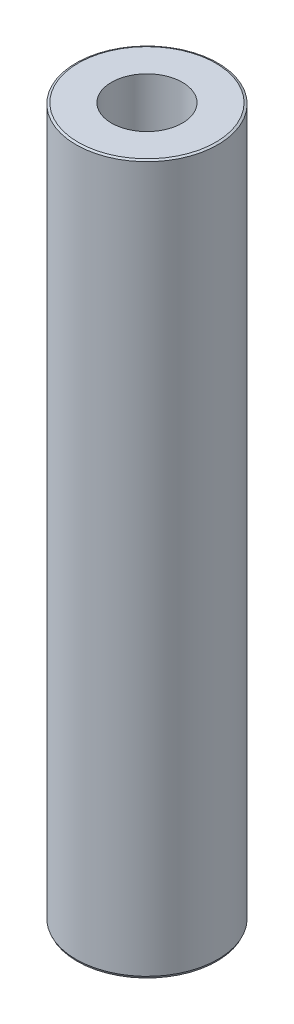
SolidWorks part; units mm, degrees
ref_plane "Front Plane" through (0, 0, 0) normal (0, 0, 1) x (1, 0, 0)
ref_plane "Top Plane" through (0, 0, 0) normal (0, 1, 0) x (1, 0, 0)
ref_plane "Right Plane" through (0, 0, 0) normal (1, 0, 0) x (0, 0, -1)
sketch "Sketch1" plane through (0, 0, 0) normal (0, 1, 0) x (1, 0, 0)
  circle A0 centre (0, 0) radius 60
  dimension "SHAFT_OD" = 120
extrude "Boss-Extrude1" add sketch "Sketch1" along normal blind 600
sketch "Sketch2" plane through (0, 0, 0) normal (0, 1, 0) x (1, 0, 0)
  circle A0 centre (0, 0) radius 29.9901
  dimension "BORE_D" = 59.9802
extrude "Cut-Extrude1" cut sketch "Sketch2" along normal through all
chamfer "Chamfer1" distance 0.8508 angle 65.144 2 edges at (0, 600, 60) (0, 0, 60) first distance on face at (0, 600, 60) first distance on face at (0, 0, 29.9901)
